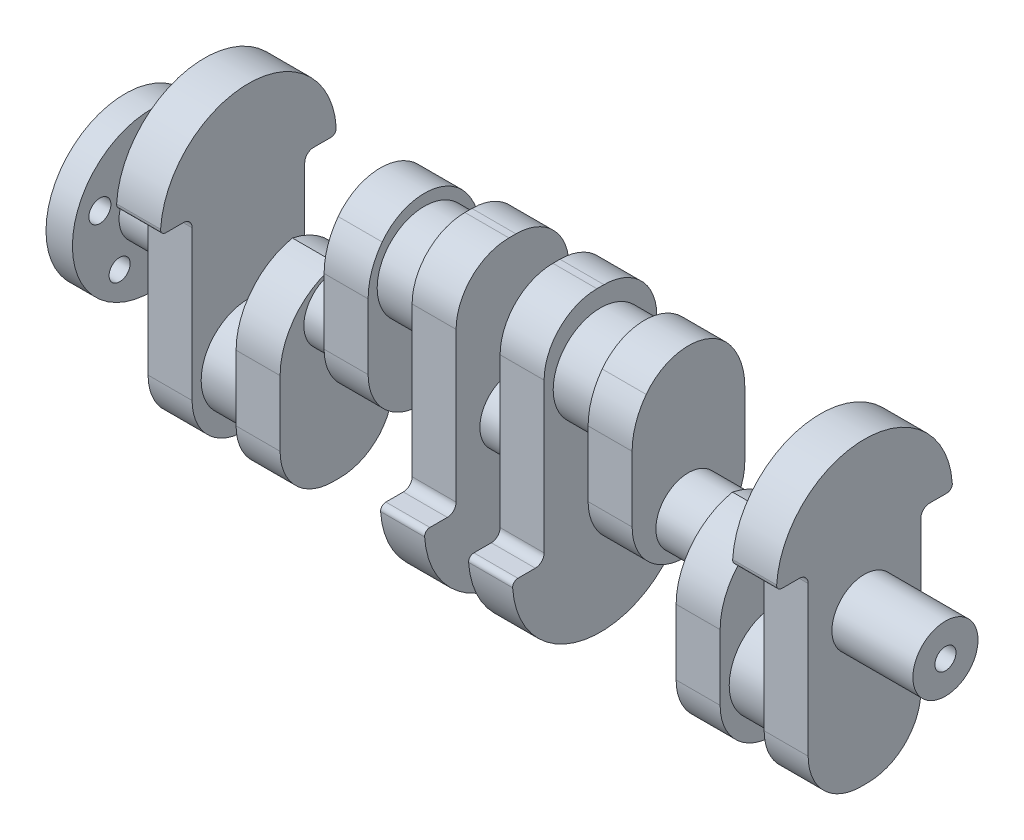
SolidWorks part; units mm, degrees
note: The reader was unsure of these and kept them because the rebuilt part matched: shared geometry of "Sketch1<5>", "Sketch1<8>", "Sketch1<9>".
ref_plane "Front Plane" through (0, 0, 0) normal (0, 0, 1) x (1, 0, 0)
ref_plane "Top Plane" through (0, 0, 0) normal (0, 1, 0) x (1, 0, 0)
ref_plane "Right Plane" through (0, 0, 0) normal (1, 0, 0) x (0, 0, -1)
sketch "Sketch1" plane through (0, 0, 0) normal (0, 0, 1) x (1, 0, 0)
  line L0 (0, 0) -> (25, 0)
  line L1 (25, 0) -> (50, 0)
  line L2 (50, 0) -> (50, -47.75)
  line L3 (25, 85) -> (50, 85)
  line L4 (25, 85) -> (25, -85)
  line L5 (25, -85) -> (50, -85)
  line L6 (50, 85) -> (50, -85)
  line L7 (37.5, -85) -> (37.5, 85) construction
  line L8 (25, 0) -> (50, 0) construction
  line L9 (50, -47.75) -> (75, -47.75)
  line L10 (75, 0) -> (100, 0)
  line L11 (87.5, 0) -> (87.5, -62.75)
  line L12 (100, 0) -> (125, 0)
  line L13 (100, 22.25) -> (75, 22.25)
  line L14 (100, 22.25) -> (100, -85)
  line L15 (100, -85) -> (75, -85)
  line L16 (75, 22.25) -> (75, -85)
  line L17 (87.5, -85) -> (87.5, 22.25) construction
  line L18 (100, -31.375) -> (75, -31.375) construction
  line L19 (125, 0) -> (150, 0)
  line L20 (150, 0) -> (150, 47.75)
  line L21 (137.5, 0) -> (137.5, 62.75)
  line L22 (150, 47.75) -> (175, 47.75)
  line L23 (150, -22.25) -> (125, -22.25)
  line L24 (150, -22.25) -> (150, 85)
  line L25 (150, 85) -> (125, 85)
  line L26 (125, -22.25) -> (125, 85)
  line L27 (137.5, 85) -> (137.5, -22.25) construction
  line L28 (150, 31.375) -> (125, 31.375) construction
  line L29 (175, 47.75) -> (200, 47.75)
  line L30 (187.5, 47.75) -> (187.5, 0)
  line L31 (200, 0) -> (225, 0)
  line L32 (200, 85) -> (175, 85)
  line L33 (200, 85) -> (200, -85)
  line L34 (200, -85) -> (175, -85)
  line L35 (175, 85) -> (175, -85)
  line L36 (187.5, -85) -> (187.5, 85) construction
  line L37 (200, 0) -> (175, 0) construction
  line L38 (225, 0) -> (250, 0)
  line L39 (250, 47.75) -> (275, 47.75)
  line L40 (250, -85) -> (225, -85)
  line L41 (250, -85) -> (250, 85)
  line L42 (250, 85) -> (225, 85)
  line L43 (225, -85) -> (225, 85)
  line L44 (237.5, 85) -> (237.5, -85) construction
  line L45 (250, 0) -> (225, 0) construction
  line L46 (275, 0) -> (300, 0)
  line L47 (287.5, 0) -> (287.5, 31.375)
  line L48 (300, 0) -> (325, 0)
  line L49 (300, -22.25) -> (275, -22.25)
  line L50 (300, -22.25) -> (300, 85)
  line L51 (300, 85) -> (275, 85)
  line L52 (275, -22.25) -> (275, 85)
  line L53 (287.5, 85) -> (287.5, -22.25) construction
  line L54 (300, 31.375) -> (275, 31.375) construction
  line L55 (325, 0) -> (350, 0)
  line L56 (337.5, 0) -> (337.5, -31.375)
  line L58 (350, 22.25) -> (325, 22.25)
  line L59 (350, 22.25) -> (350, -85)
  line L60 (350, -85) -> (325, -85)
  line L61 (325, 22.25) -> (325, -85)
  line L62 (337.5, -85) -> (337.5, 22.25) construction
  line L63 (350, -31.375) -> (325, -31.375) construction
  line L64 (375, 0) -> (400, 0)
  line L65 (75, -47.75) -> (375, -47.75)
  line L66 (400, 85) -> (375, 85)
  line L67 (400, 85) -> (400, -85)
  line L68 (400, -85) -> (375, -85)
  line L69 (375, 85) -> (375, -85)
  line L70 (387.5, -85) -> (387.5, 85) construction
  line L71 (400, 0) -> (375, 0) construction
  line L72 (50, -47.75) -> (75, -47.75)
  line L73 (50, -47.75) -> (50, -20.9)
  line L74 (50, -20.9) -> (75, -20.9)
  line L75 (75, -47.75) -> (75, -20.9)
  line L76 (150, 47.75) -> (175, 47.75)
  line L77 (150, 47.75) -> (150, 74.6)
  line L78 (150, 74.6) -> (175, 74.6)
  line L79 (175, 47.75) -> (175, 74.6)
  line L80 (275, 47.75) -> (250, 47.75)
  line L81 (275, 47.75) -> (275, 74.6)
  line L82 (275, 74.6) -> (250, 74.6)
  line L83 (250, 47.75) -> (250, 74.6)
  line L88 (100, 0) -> (125, 0)
  line L89 (100, 0) -> (100, 18.4983)
  line L90 (100, 18.4983) -> (125, 18.4983)
  line L91 (125, 0) -> (125, 18.4983)
  line L92 (25, 0) -> (0, 0)
  line L93 (25, 0) -> (25, 18.4983)
  line L94 (25, 18.4983) -> (0, 18.4983)
  line L95 (0, 0) -> (0, 18.4983)
  line L96 (200, 0) -> (225, 0)
  line L97 (200, 0) -> (200, 18.4983)
  line L98 (200, 18.4983) -> (225, 18.4983)
  line L99 (225, 0) -> (225, 18.4983)
  line L100 (300, 0) -> (325, 0)
  line L101 (300, 0) -> (300, 18.4983)
  line L102 (300, 18.4983) -> (325, 18.4983)
  line L103 (325, 0) -> (325, 18.4983)
  line L104 (400, 0) -> (425, 0)
  line L105 (400, 0) -> (400, 18.4983)
  line L106 (400, 18.4983) -> (425, 18.4983)
  line L107 (425, 0) -> (425, 18.4983)
  line L108 (375, -47.75) -> (350, -47.75)
  line L110 (350, -47.75) -> (375, -47.75)
  line L111 (350, -47.75) -> (350, -20.9)
  line L112 (350, -20.9) -> (375, -20.9)
  line L113 (375, -47.75) -> (375, -20.9)
  point P3 (37.5, 0)
  point P14 (87.5, -31.375)
  point P23 (137.5, 31.375)
  point P36 (237.5, 0)
  point P60 (387.5, 0)
  dimension "D1" = 25
  dimension "D2" = 25
  dimension "D3" = 170
  dimension "D4" = 47.75
  dimension "D5" = 25
  dimension "D6" = 25
  dimension "D7" = 107.25
  dimension "D8" = 25
  dimension "D9" = 25
  dimension "D10" = 47.75
  dimension "D11" = 25
  dimension "D12" = 25
  dimension "D13" = 25
  dimension "D14" = 25
  dimension "D15" = 25
  dimension "D16" = 25
  dimension "D17" = 25
  dimension "D18" = 25
  dimension "D19" = 26.85
  dimension "D20" = 25
  dimension "D21" = 26.85
  dimension "D22" = 170
  dimension "D23" = 25
  dimension "D24" = 25
  dimension "D25" = 25
  dimension "D26" = 25
  dimension "D27" = 25
  dimension "D28" = 170
  dimension "D29" = 170
  dimension "D30" = 107.25
  dimension "D31" = 107.25
  dimension "D32" = 107.25
  dimension "D33" = 26.85
  dimension "D34" = 26.85
  dimension "D35" = 25
revolve "Revolve1" add sketch "Sketch1" angle 360 about L22
revolve "Revolve3" add sketch "Sketch1<5>" angle 360 about L9
sketch "Sketch1<5>" plane through (0, 0, 0) normal (0, 0, 1) x (1, 0, 0) same geometry as "Sketch1"
revolve "Revolve4" add sketch "Sketch1<8>" angle 360 about L10
sketch "Sketch1<8>" plane through (0, 0, 0) normal (0, 0, 1) x (1, 0, 0) same geometry as "Sketch1"
extrude "Boss-Extrude1" add sketch "Sketch1<9>" along normal mid plane 64
sketch "Sketch1<9>" plane through (0, 0, 0) normal (0, 0, 1) x (1, 0, 0) same geometry as "Sketch1"
fillet "Fillet1" radius 30 16 edges at (387.5, -85, -32) (387.5, -85, 32) (337.5, -85, -32) (337.5, -85, 32) (287.5, -22.25, -32) (287.5, -22.25, 32) (237.5, 85, -32) (237.5, 85, 32) (187.5, 85, -32) (187.5, 85, 32) (137.5, -22.25, 32) (137.5, -22.25, -32) (87.5, -85, -32) (87.5, -85, 32) (37.5, -85, 32) (37.5, -85, -32)
fillet "Fillet3" radius 40 8 edges at (287.5, 85, -32) (287.5, 85, 32) (137.5, 85, -32) (137.5, 85, 32) (337.5, 22.25, -32) (337.5, 22.25, 32) (87.5, 22.25, -32) (87.5, 22.25, 32)
sketch "Sketch2" plane through (0, 0, 0) normal (0, 0, 1) x (1, 0, 0)
  line L0 (50, 85) -> (50, -55) construction
  line L1 (25, 85) -> (50, 85)
  line L2 (25, 85) -> (25, 35)
  line L3 (25, 35) -> (50, 35)
  line L4 (50, 85) -> (50, 35)
  line L5 (175, 55) -> (175, -85) construction
  line L6 (200, -85) -> (175, -85)
  line L7 (200, -85) -> (200, -35)
  line L8 (200, -35) -> (175, -35)
  line L9 (175, -85) -> (175, -35)
  line L10 (225, -85) -> (225, 55) construction
  line L11 (250, -85) -> (225, -85)
  line L12 (250, -85) -> (250, -35)
  line L13 (250, -35) -> (225, -35)
  line L14 (225, -85) -> (225, -35)
  line L15 (400, 85) -> (400, -55) construction
  line L16 (375, 85) -> (400, 85)
  line L17 (375, 85) -> (375, 35)
  line L18 (375, 35) -> (400, 35)
  line L19 (400, 85) -> (400, 35)
  dimension "D1" = 50
  dimension "D2" = 50
extrude "Boss-Extrude2" add sketch "Sketch2" along normal mid plane 100
fillet "Fillet12" radius 50 8 edges at (50, 85, 0) (25, 85, 0) (25, 60, -50) (50, 60, -50) (37.5, 85, -50) (25, 60, 50) (50, 60, 50) (37.5, 85, 50)
fillet "Fillet13" radius 50 8 edges at (375, 60, -50) (400, 60, -50) (387.5, 85, -50) (375, 60, 50) (400, 60, 50) (387.5, 85, 50) (400, 85, 0) (375, 85, 0)
fillet "Fillet14" radius 50 8 edges at (200, -60, -50) (175, -60, -50) (187.5, -85, -50) (200, -60, 50) (175, -60, 50) (187.5, -85, 50) (175, -85, 0) (200, -85, 0)
fillet "Fillet15" radius 50 8 edges at (250, -60, -50) (225, -60, -50) (237.5, -85, -50) (250, -60, 50) (225, -60, 50) (237.5, -85, 50) (225, -85, 0) (250, -85, 0)
fillet "Fillet16" radius 30 2 edges at (287.5, 84.1918, 0) (137.5, 84.1918, 0)
fillet "Fillet17" radius 3 8 edges at (37.5, 35, -50) (37.5, 35, 50) (187.5, -35, -50) (187.5, -35, 50) (237.5, -35, -50) (237.5, -35, 50) (387.5, 35, -50) (387.5, 35, 50)
fillet "Fillet18" radius 5 8 edges at (237.5, -35, -32) (237.5, -35, 32) (187.5, -35, -32) (187.5, -35, 32) (387.5, 35, -32) (387.5, 35, 32) (37.5, 35, -32) (37.5, 35, 32)
sketch "Sketch3" plane through (425, 0, 0) normal (1, 0, 0) x (0, 0, -1)
  circle A0 centre (0, 0) radius 18.4983
extrude "Boss-Extrude3" add sketch "Sketch3" along normal blind 21
sketch "Sketch4" plane through (0, 0, 0) normal (-1, 0, 0) x (0, 0, 1)
  circle A0 centre (0, 0) radius 18.4983
extrude "Boss-Extrude4" add sketch "Sketch4" along normal blind 5
sketch "Sketch5" plane through (-5, 0, 0) normal (-1, 0, 0) x (0, 0, 1)
  circle A0 centre (0, 0) radius 45
  dimension "D1" = 90
extrude "Boss-Extrude5" add sketch "Sketch5" along normal blind 15
sketch "Sketch6" plane through (-20, 0, 0) normal (-1, 0, 0) x (0, 0, 1)
  line L1 (0, 30.9017) -> (-29.3893, 9.5492)
  line L2 (-29.3893, 9.5492) -> (-18.1636, -25)
  line L3 (-18.1636, -25) -> (18.1636, -25)
  line L4 (18.1636, -25) -> (29.3893, 9.5492)
  line L5 (29.3893, 9.5492) -> (0, 30.9017)
  circle A0 centre (0, 0) radius 25 construction
  circle A1 centre (0, 30.9017) radius 6
  circle A2 centre (-29.3893, 9.5492) radius 6
  circle A3 centre (-18.1636, -25) radius 6
  circle A4 centre (18.1636, -25) radius 6
  circle A5 centre (29.3893, 9.5492) radius 6.2524
  dimension "D1" = 12
  dimension "D2" = 12
  dimension "D3" = 12
  dimension "D4" = 12
extrude "Cut-Extrude1" cut sketch "Sketch6" against normal blind 15 contours L1 A2 L2 | L5 A1 L1 | L4 A5 L5 | L3 A4 L4 | L2 A3 L3 | L3 A3 L2 | L2 A2 L1 | L4 A4 L3 | L5 A5 L4 | L1 A1 L5
sketch "Sketch7" plane through (446, 0, 0) normal (1, 0, 0) x (0, 0, -1)
  circle A0 centre (0, 0) radius 6
  dimension "D1" = 12
extrude "Cut-Extrude2" cut sketch "Sketch7" against normal blind 20
